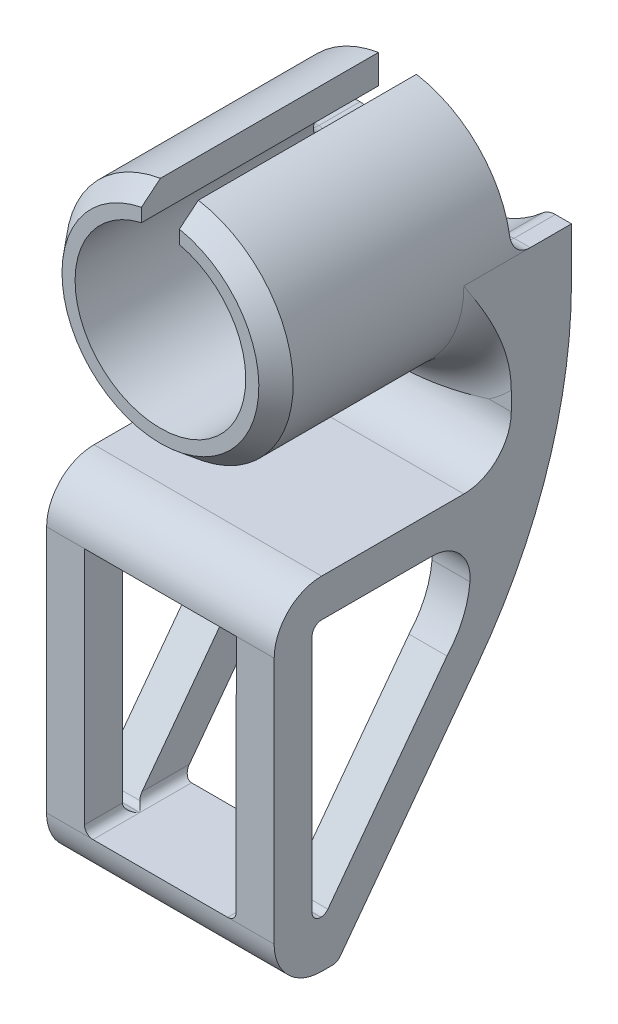
SolidWorks part; units mm, degrees
material "ABS PC"
ref_plane "Front Plane" through (0, 0, 0) normal (0, 0, 1) x (1, 0, 0)
ref_plane "Top Plane" through (0, 0, 0) normal (0, 1, 0) x (1, 0, 0)
ref_plane "Right Plane" through (0, 0, 0) normal (1, 0, 0) x (0, 0, -1)
sketch "Sketch1" plane through (0, 0, 0) normal (0, 0, 1) x (1, 0, 0)
  circle A0 centre (0, 0) radius 12
  dimension "D1" = 24
extrude "Boss-Extrude1" add sketch "Sketch1" along normal blind 25
sketch "Sketch2" plane through (0, 0, 25) normal (0, 0, 1) x (1, 0, 0)
  line L3 (-2, 12) -> (2, 12)
  line L7 (-2, 8.775) -> (-2, 12)
  line L10 (2, 8.775) -> (2, 12)
  arc A0 (-2, 8.775) -> (2, 8.775) centre (0, 0) ccw
  point P1 (0, 12)
  dimension "D1" = 18
  dimension "D4" = 4
  dimension "D6" = 12
extrude "Cut-Extrude1" cut sketch "Sketch2" against normal up to surface (25 mm away) up to face at (12, 0, 0)
sketch "Sketch3" plane through (0, 0, 0) normal (0, 0, -1) x (-1, 0, 0)
  line L0 (-9.5028, 0) -> (-12, 0)
  line L1 (9.5028, 0) -> (12, 0)
  line L2 (12, 0) -> (12, -19)
  line L3 (-12, 0) -> (-12, -19)
  line L4 (12, -19) -> (-12, -19)
  arc A0 (-9.5028, 0) -> (9.5028, 0) centre (0, 9.5) ccw
  circle A1 centre (0, 0) radius 12 construction
  point P11 (0, -3.937)
  dimension "D1" = 19
  dimension "D2" = 13.437
  dimension "D3" = 3.937
extrude "Boss-Extrude2" add sketch "Sketch3" along normal blind 6.35
fillet "Fillet1" radius 7.62 1 edges at (0, -9, 0)
fillet "Fillet2" [suppressed] radius 7.62
chamfer "Chamfer1" distance 2 angle 39 1 edges at (0, -12, 25) first distance on face at (0, 2.526, 8.3333)
sketch "Sketch6" plane through (0, -19, 0) normal (0, -1, 0) x (1, 0, 0)
  line L0 (-12, 25) -> (-12, -6.35)
  line L1 (-12, 25) -> (12, 25)
  line L2 (-12, -6.35) -> (12, -6.35)
  line L3 (12, 25) -> (12, -6.35)
  line L6 (10.3804, 25) -> (-10.3804, 25) construction
  point P1 (0, 0)
  point P9 (0, -6.35)
extrude "Boss-Extrude3" add sketch "Sketch6" along normal blind 3
sketch "Sketch7" plane through (12, 0, 0) normal (1, 0, 0) x (0, 0, -1)
  line L0 (-25, -22) -> (6.35, -22)
  line L2 (6.35, -22) -> (-18.3486, -55.1118)
  line L3 (-25.0132, -55.1118) -> (-18.3486, -55.1118)
  line L4 (-25, -22) -> (-25.0132, -55.1118)
extrude "Boss-Extrude4" add sketch "Sketch7" against normal up to surface (24 mm away) up to face at (-12, -13.6667, 6.2167)
fillet "Fillet3" radius 50 1 edges at (0, -22, -6.35)
fillet "Fillet7" radius 5 2 edges at (0, -19, 0) (0, -12, 0)
fillet "Fillet8" radius 5 1 edges at (0, -55.1118, 25.0132)
fillet "Fillet9" radius 5 1 edges at (0, -19, 25)
sketch "Sketch8" plane through (12, 0, 0) normal (1, 0, 0) x (0, 0, -1)
  line L29 (-5, -23) -> (-20.0008, -23)
  line L30 (-21.0008, -23.9996) -> (-21.0112, -50.1114)
  line L31 (-20.319, -51.0632) -> (-6.7779, -32.9096)
  line L32 (-5, -23) -> (-20.0008, -23)
  line L33 (-21.0008, -23.9996) -> (-21.0112, -50.1114)
  line L34 (-20.319, -51.0632) -> (-6.7779, -32.9096)
  arc A12 (-5, -23) -> (-6.7779, -32.9096) centre (-13.828, -26.5305) cw
  arc A16 (-20.0008, -23) -> (-21.0008, -23.9996) centre (-20.0008, -24) ccw
  arc A17 (-21.0112, -50.1114) -> (-20.319, -51.0632) centre (-20.0112, -50.1118) ccw
  arc A18 (-6.7779, -32.9096) -> (-0.7142, -21.914) centre (-43.65, -5.406) ccw
  arc A19 (-5, -23) -> (-0.7142, -21.914) centre (-5, -14) ccw
  arc A20 (-20.0008, -23) -> (-21.0008, -23.9996) centre (-20.0008, -24) ccw
  arc A21 (-21.0112, -50.1114) -> (-20.319, -51.0632) centre (-20.0112, -50.1118) ccw
  dimension "D1" = 4
extrude "Cut-Extrude2" cut sketch "Sketch8" against normal up to surface (24 mm away) up to face at (-12, -22.5457, 8.155)
fillet "Fillet10" radius 1 1 edges at (0, -55.1118, 18.3486)
fillet "Fillet12" radius 2 2 edges at (-9.5028, 0, -3.175) (9.5028, 0, -3.175)
fillet "Fillet13" radius 2 4 edges at (-9.5981, -0.1265, 0) (-11.1491, 0, 0) (9.5981, -0.1265, 0) (11.1491, 0, 0)
sketch "Sketch9" plane through (0, 0.0099, 24.9913) normal (0, 0.0004, 1) x (1, 0, 0)
  line L0 (12, -24.0079) -> (-12, -24.0079) construction
  line L1 (-8, -50.1197) -> (8, -50.1197)
  line L2 (-8, -50.1197) -> (-8, -24.0079)
  line L3 (-8, -24.0079) -> (8, -24.0079)
  line L4 (8, -50.1197) -> (8, -24.0079)
  line L5 (-12, -50.1197) -> (12, -50.1197) construction
  line L6 (12, -55.1197) -> (-12, -55.1197) construction
  line L7 (-12, -50.1197) -> (-12, -24.0079) construction
  point P9 (0, -55.1197)
  point P12 (0, -24.0079)
  dimension "D1" = 4
extrude "Cut-Extrude3" cut sketch "Sketch9" against normal up to surface (10.3905 mm away) up to face at (0, -45.0054, 10.8102)
fillet "Fillet14" [suppressed] radius 0.5
fillet "Fillet15" radius 4 1 edges at (0, -23, 5)
sketch "Sketch10" plane through (0, -50.1197, 0.0199) normal (0, 1, -0.0004) x (1, 0, 0)
  line L1 (-12, -19.5895) -> (12, -19.5895)
  line L2 (-12, -19.5895) -> (-12, -20.9913)
  line L3 (-12, -20.9913) -> (12, -20.9913)
  line L4 (12, -19.5895) -> (12, -20.9913)
  point P4 (0, 0)
  point P5 (0, 0)
  point P6 (0, 0)
  point P9 (0, 0)
extrude "Boss-Extrude5" add sketch "Sketch10" against normal up to next
fillet "Fillet16" radius 0.9 8 edges at (10, -50.1114, 21.0112) (10, -50.1119, 19.6094) (8, -50.1106, 23.0112) (8, -50.1129, 17.115) (-8, -50.1129, 17.115) (-8, -50.1106, 23.0112) (-10, -50.1114, 21.0112) (-10, -50.1119, 19.6094)
